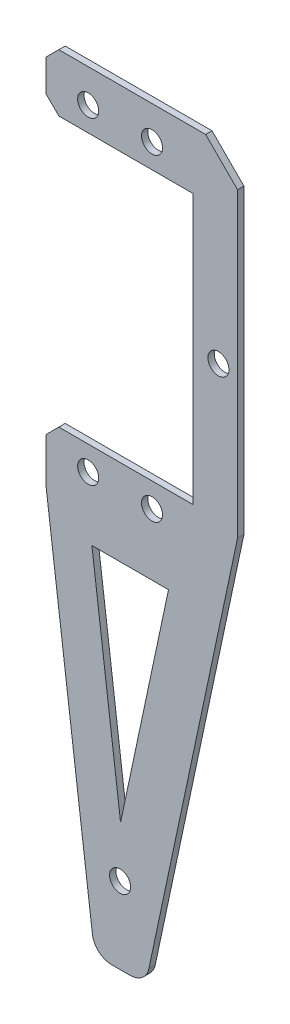
SolidWorks part; units mm, degrees
ref_plane "前视基准面" through (0, 0, 0) normal (0, 0, 1) x (1, 0, 0)
ref_plane "上视基准面" through (0, 0, 0) normal (0, 1, 0) x (1, 0, 0)
ref_plane "右视基准面" through (0, 0, 0) normal (1, 0, 0) x (0, 0, -1)
sketch "草图1" plane through (0, 0, 0) normal (0, 0, 1) x (1, 0, 0)
  line L0 (-23, 0) -> (0, 0)
  line L1 (0, 0) -> (0, 42.2)
  line L2 (0, 42.2) -> (-23, 42.2)
  line L3 (-23, 42.2) -> (-23, 51.2)
  line L4 (-23, 51.2) -> (7, 51.2)
  line L5 (7, 51.2) -> (7, -1.0533)
  line L7 (-23, -9) -> (-23, 0)
  line L8 (-23, -9) -> (-15.4, -68.8)
  line L9 (-15.4, -68.8) -> (-7.4, -68.8)
  line L11 (-15.8178, -13.4692) -> (-3.8178, -13.4692)
  line L12 (-3.8178, -13.4692) -> (-11.3276, -48.8)
  line L13 (-11.3276, -48.8) -> (-15.8178, -13.4692)
  line L14 (-7.4, -68.8) -> (7, -1.0533)
  point P8 (0, 0)
  point P13 (-11.4, -68.8)
  dimension "D1" = 23
  dimension "D2" = 9
  dimension "D3" = 9
  dimension "D4" = 23
  dimension "D5" = 42.2
  dimension "D6" = 30
  dimension "D7" = 120
  dimension "D8" = 8
  dimension "D9" = 12
  dimension "D10" = 102
  dimension "D11" = 20
  dimension "D12" = 8
base flange "基体-法兰1" sketch "草图1" thickness 1 reverse thickness direction no parameters "D1"=0.7366
hole_wizard "Ø3.3 (3.3) 直径孔1" positions "草图6" profile "草图7" hole size "Ø3.3" standard "GB" end condition through all
sketch "草图6" plane through (0, 0, 0) normal (0, 0, 1) x (1, 0, 0)
  line L0 (0, 0) -> (-23, 0) construction
  line L1 (0, 42.2) -> (0, 0) construction
  line L2 (7, -1.0533) -> (7, 51.2) construction
  line L3 (-15.4, -68.8) -> (-7.4, -68.8) construction
  point P0 (-6.4, 46)
  point P2 (-16.4, 46)
  point P4 (-16.4, -3.8)
  point P6 (-6.4, -3.8)
  point P20 (4, 21.1)
  point P22 (-11.4, -56.8)
  point P28 (0, 0)
  point P29 (0, 21.1)
  point P32 (0, 0)
  point P33 (0, 0)
  point P34 (-11.4, -68.8)
  dimension "D1" = 10
  dimension "D2" = 49.8
  dimension "D3" = 3.8
  dimension "D4" = 6.4
  dimension "D5" = 3
  dimension "D6" = 12
sketch "草图7" plane through (-6.4, 46, 0) normal (1, 0, 0) x (0, -1, 0)
  line L0 (0, 0) -> (0, 1)
  line L1 (0, 1) -> (1.65, 1)
  line L2 (1.65, 1) -> (1.65, 0)
  line L5 (1.65, 0) -> (0, 0)
  line L11 (0, -6.35) -> (0, 107.95) construction
  dimension "通孔孔直径" = 3.3
  dimension "通孔孔深度" = 1
chamfer "倒角2" distance 5 angle 45 1 edges at (7, 51.2, -0.5)
fillet "圆角1" radius 3 2 edges at (-7.4, -68.8, -0.5) (-15.4, -68.8, -0.5)
chamfer "倒角3" distance 2 angle 45 3 edges at (-23, 0, -0.5) (-23, 42.2, -0.5) (-23, 51.2, -0.5)
sketch "折弯-线1" [suppressed] plane through (0, 0, 0) normal (0, 1, 0) x (1, 0, 0)
sketch "边界框1" [suppressed] plane through (0, 0, 0) normal (0, 1, 0) x (1, 0, 0)
sheet metal parameters "钣金1" thickness 1 parameters "D1"=0.7366
flat pattern "平板型式1" [suppressed]
sketch "折弯-线2" plane through (0, 0, 0) normal (0, 1, 0) x (1, 0, 0)
sketch3d "边界框2" [suppressed]
  line L0 (-7, 51.2, 0) -> (-7, -9, 0) construction
  line L1 (23, 51.2, 0) -> (23, -9, 0) construction
  line L2 (-7, 51.2, 0) -> (23, 51.2, 0) construction
  line L3 (-7, -9, 0) -> (23, -9, 0) construction
sheet metal parameters "钣金2" thickness 1 parameters "D1"=0.7366
flat pattern "平板型式1"
sketch "折弯-线2" plane through (0, 0, 0) normal (0, 1, 0) x (1, 0, 0)
sketch3d "边界框2" [suppressed]
  line L0 (7, -68.8, 0) -> (7, 51.2, 0) construction
  line L1 (-23, -68.8, 0) -> (-23, 51.2, 0) construction
  line L2 (7, -68.8, 0) -> (-23, -68.8, 0) construction
  line L3 (7, 51.2, 0) -> (-23, 51.2, 0) construction
